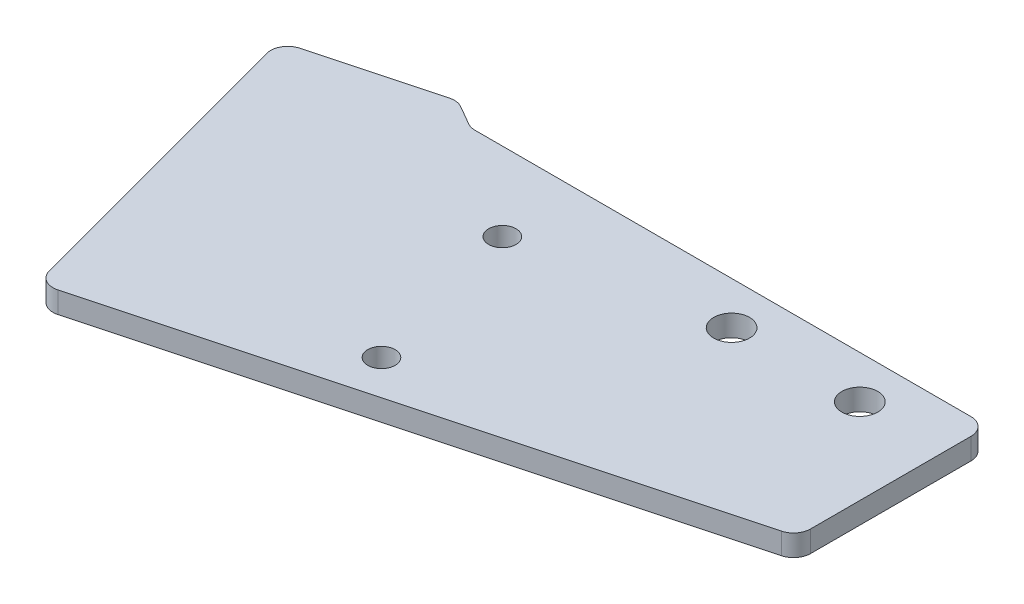
SolidWorks part; units mm, degrees
material "Thornel Mat VMA"
ref_plane "前视基准面" through (0, 0, 0) normal (0, 0, 1) x (1, 0, 0)
ref_plane "上视基准面" through (0, 0, 0) normal (0, 1, 0) x (1, 0, 0)
ref_plane "右视基准面" through (0, 0, 0) normal (1, 0, 0) x (0, 0, -1)
sketch "草图1" plane through (0, 0, 0) normal (0, 1, 0) x (1, 0, 0)
  line L0 (-7.5, 0) -> (7.5, 0) construction
  line L1 (-17.5, 5) -> (17.5, 5)
  line L2 (-17.5, 5) -> (-17.5, -5)
  line L3 (-17.5, -5) -> (17.5, -5)
  line L4 (17.5, 5) -> (17.5, -5)
  line L5 (-17.5, 5) -> (17.5, -5) construction
  line L6 (-17.5, -5) -> (17.5, 5) construction
  circle A0 centre (-7.5, 0) radius 2.1
  circle A1 centre (7.5, 0) radius 2.1
  point P0 (0, 0)
  dimension "D4" = 4.2
  dimension "D1" = 15
  dimension "D2" = 10
  dimension "D3" = 35
extrude "凸台-拉伸1" add sketch "草图1" along normal blind 2.5
sketch "草图2" plane through (0, 2.5, 0) normal (0, 1, 0) x (1, 0, 0)
  line L1 (-52.6515, -36.0884) -> (-63.0042, 2.5486)
  line L3 (-17.5, 5) -> (-17.5, -5)
  line L4 (-17.5, 5) -> (-17.5, -5) construction
  line L5 (-17.5, -5) -> (17.5, -5)
  line L6 (-57.8279, -16.7699) -> (-28.8501, -9.0053) construction
  line L7 (-17.5, -5) -> (-12.0826, -25.218)
  line L8 (-17.5, -5) -> (17.5, -5) construction
  line L9 (-63.0042, 2.5486) -> (-17.5, 14.7414)
  line L10 (-17.5, 14.7414) -> (-17.5, 5)
  line L11 (-52.6515, -36.0884) -> (17.5, -17.2914)
  line L13 (17.5, -5) -> (17.5, -17.2914)
  line L14 (-30.1442, -4.1757) -> (-24.9678, -23.4942) construction
  line L15 (-28.8501, -9.0053) -> (-19.5, -6.5) construction
  line L16 (17.5, -5) -> (17.5, 5) construction
  circle A0 centre (-30.1442, -4.1757) radius 1.6
  circle A1 centre (-24.9678, -23.4942) radius 1.6
  point P17 (-17.5, 5)
  line M9 (-17.5, 5) -> (-17.5, -5)
  dimension "D7" = 3.2
  dimension "D1" = 40
  dimension "D2" = 30
  dimension "D3" = 12
  dimension "D4" = 5
  dimension "D5" = 15
  dimension "D6" = 105
extrude "凸台-拉伸2" add sketch "草图2" against normal up to surface (2.5 mm away) contours L1 L11 L7 L10 L9 A1 A0 M9 | L3 L10 L9 L1 L11 L13 L5 region at (-37.1139, 2.5, 10.7692) up to face at (0, 0, 0)
extrude "切除-拉伸1" cut sketch "草图2<3>" against normal through all contours A0 | A1 region at (-30.1442, 2.5, 4.1757) region at (-24.9678, 2.5, 23.4942)
sketch "草图2<3>" plane through (0, 2.5, 0) normal (0, 1, 0) x (1, 0, 0) same geometry as "草图2"
chamfer "倒角1" distance 30 angle 45 1 edges at (-17.5, 1.25, -14.7414) first distance on face at (-40.2521, 1.25, -8.645)
fillet "圆角1" radius 2 6 edges at (17.5, 1.25, 17.2914) (-52.6515, 1.25, 36.0884) (-63.0042, 1.25, -2.5486) (-46.4778, 1.25, -6.9769) (-43.0538, 1.25, -5) (17.5, 1.25, -5)
